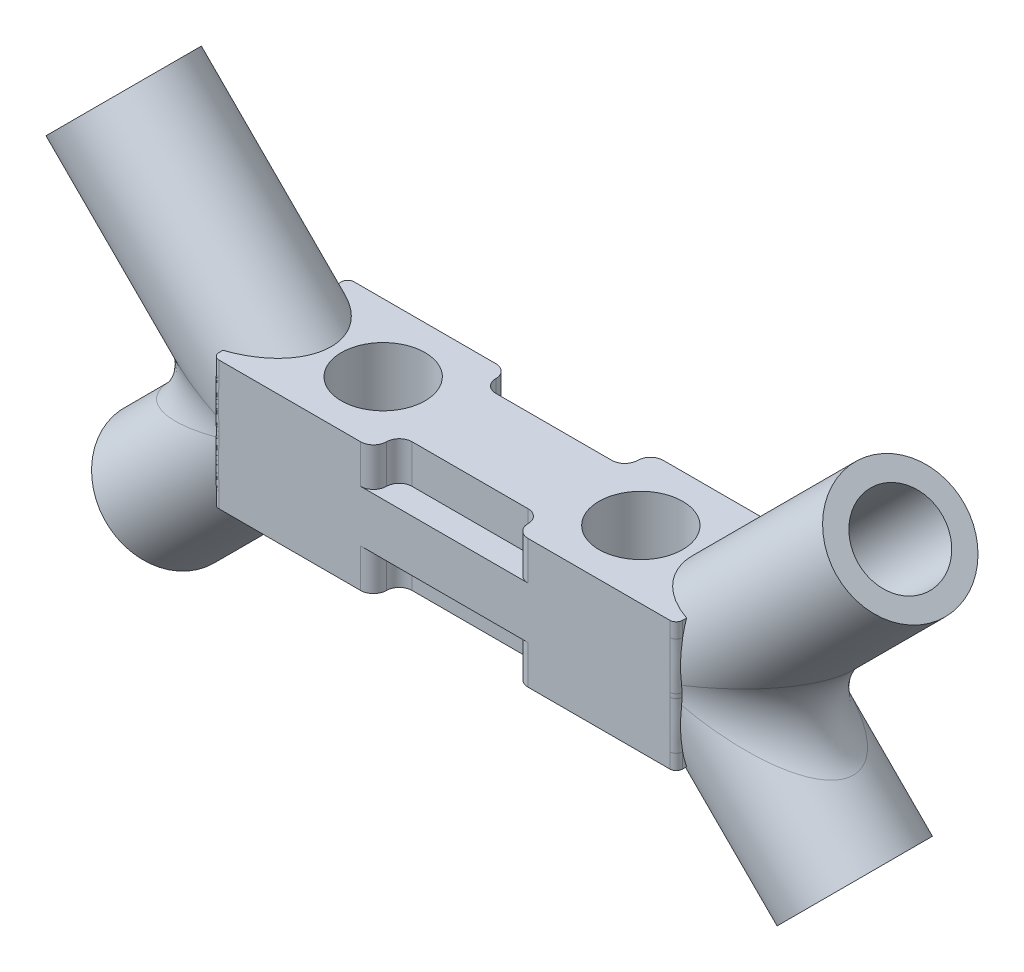
SolidWorks part; units mm, degrees
ref_plane "Alzado" through (0, 0, 0) normal (0, 0, 1) x (1, 0, 0)
ref_plane "Planta" through (0, 0, 0) normal (0, 1, 0) x (1, 0, 0)
ref_plane "Vista lateral" through (0, 0, 0) normal (1, 0, 0) x (0, 0, -1)
sketch "Croquis1" plane through (0, 0, 0) normal (0, 1, 0) x (1, 0, 0)
  line L0 (0, 0) -> (-36, 0) construction
  line L1 (-11, 6.5) -> (11, 6.5)
  line L3 (-11, -6.5) -> (11, -6.5)
  line L5 (-11, 6.5) -> (11, -6.5) construction
  line L6 (-11, -6.5) -> (11, 6.5) construction
  line L7 (-36, -10.5) -> (-36, 10.5)
  line L10 (0, 0) -> (0, -6.5) construction
  line L12 (36, -10.5) -> (36, 10.5)
  line L14 (-36, 10.5) -> (-11, 10.5)
  line L15 (-11, 10.5) -> (-11, 6.5)
  line L16 (-36, -10.5) -> (-11, -10.5)
  line L17 (-11, -10.5) -> (-11, -6.5)
  line L18 (36, 10.5) -> (11, 10.5)
  line L19 (11, 10.5) -> (11, 6.5)
  line L20 (36, -10.5) -> (11, -10.5)
  line L21 (11, -10.5) -> (11, -6.5)
  point P4 (0, 0)
  point P14 (-36, 0)
  point P16 (0, 6.5)
  dimension "D1" = 25
  dimension "D4" = 21
  dimension "D2" = 22
  dimension "D3" = 13
extrude "Saliente-Extruir2" add sketch "Croquis1" along normal mid plane 20
sketch "Croquis2" plane through (0, 0, 0) normal (0, 1, 0) x (1, 0, 0)
  line L0 (-36, -5) -> (-50.1421, -19.1421)
  line L2 (-36, -5) -> (-36, 5)
  line L3 (36, -5) -> (36, 5)
  line L4 (36, -10.5) -> (36, 10.5) construction
  line L5 (36, -5) -> (50.1421, -19.1421)
  line L6 (36, 5) -> (50.1421, 19.1421)
  line L7 (0, 0) -> (0, -6.5) construction
  line L8 (-11, -6.5) -> (11, -6.5) construction
  line L9 (-36, 5) -> (-50.1421, 19.1421)
  point P15 (36, 0)
  dimension "D2" = 10
  dimension "D5" = 45
  dimension "D6" = 45
  dimension "D7" = 20
ref_plane "Plano1" through (50.1421, 0, 0) normal (1, 0, 0) x (0, 0, -1)
sketch "Croquis22" plane through (0, 0, 0) normal (0, 0, 1) x (1, 0, 0)
  line L0 (-60.2843, 28.2843) -> (-32, 0)
  line L1 (-32, 0) -> (-53.2132, -21.2132)
  line L2 (-32, 0) -> (-36, 0) construction
  line L3 (-36, 10) -> (-36, -10) construction
  line L4 (32, 0) -> (53.2132, -21.2132)
  line L5 (60.2843, 28.2843) -> (32, 0)
  line L6 (0, 0) -> (0, -10) construction
  line L7 (-11, -10) -> (11, -10) construction
  dimension "D6" = 45
  dimension "D2" = 45
  dimension "D3" = 40
  dimension "D4" = 4
  dimension "D5" = 30
ref_plane "Plano2" through (-60.2843, 28.2843, 0) normal (0.7071, -0.7071, 0) x (-0.7071, -0.7071, 0)
sketch "Croquis33" plane through (-60.2843, 28.2843, 0) normal (0.7071, -0.7071, 0) x (-0.7071, -0.7071, 0)
  circle A0 centre (0, 0) radius 9.85
  dimension "D1" = 19.7
ref_plane "Plano3" through (60.2843, 28.2843, 0) normal (-0.7071, -0.7071, 0) x (0, 0, 1)
sketch "Croquis34" plane through (60.2843, 28.2843, 0) normal (-0.7071, -0.7071, 0) x (0, 0, 1)
  circle A0 centre (0, 0) radius 9.85
  dimension "D2" = 19.7
sketch "Croquis35" plane through (0, 0, 0) normal (0, 1, 0) x (1, 0, 0)
  line L0 (-20, 0) -> (20, 0) construction
  circle A0 centre (-20, 0) radius 6.5
  circle A1 centre (20, 0) radius 6.5
  point P4 (0, 0)
  dimension "D1" = 13
  dimension "D2" = 40
extrude "Huecos frontales" cut sketch "Croquis35" against normal mid plane 30 contours A1 | A0
extrude "Saliente-Extruir3" add sketch "Croquis33" along normal up to body separate body
extrude "Saliente-Extruir5" add sketch "Croquis34" along normal up to body separate body
ref_plane "Plano4" through (-53.2132, -21.2132, 0) normal (-0.7071, -0.7071, 0) x (0, 0, 1)
ref_plane "Plano5" through (53.2132, -21.2132, 0) normal (0.7071, -0.7071, 0) x (0, 0, -1)
sketch "Croquis36" plane through (-53.2132, -21.2132, 0) normal (-0.7071, -0.7071, 0) x (0, 0, 1)
  circle A0 centre (0, 0) radius 9.85
  dimension "D2" = 19.7
extrude "Saliente-Extruir6" add sketch "Croquis36" against normal up to body separate body
sketch "Croquis37" plane through (53.2132, -21.2132, 0) normal (0.7071, -0.7071, 0) x (0, 0, -1)
  circle A0 centre (0, 0) radius 9.85
  dimension "D1" = 19.7
extrude "Saliente-Extruir7" add sketch "Croquis37" against normal up to body separate body
fillet "Redondeo2" radius 2 8 edges at (11, 0, -10.5) (11, 0, -6.5) (-11, 0, -6.5) (-11, 0, -10.5) (11, 0, 6.5) (11, 0, 10.5) (-11, 0, 6.5) (-11, 0, 10.5)
fillet "Redondeo4" radius 1 4 edges at (-36, 0, 10.5) (36, 0, 10.5) (-36, 0, -10.5) (36, 0, -10.5)
sketch "Croquis38" plane through (-44.2843, 44.2843, 0) normal (-0.7071, 0.7071, 0) x (0, 0, 1)
  circle A0 centre (0, -22.6274) radius 6.5
  circle A1 centre (0, -22.6274) radius 9.85
  circle A2 centre (0, -22.6274) radius 9.85
  dimension "D2" = 13
  dimension "D1" = 0
extrude "Cortar-Extruir3" cut sketch "Croquis38" against normal blind 30 contours A0
sketch "Croquis40" plane through (-37.2132, -37.2132, 0) normal (-0.7071, -0.7071, 0) x (0, 0, 1)
  circle A0 centre (0, 22.6274) radius 6.53
  circle A1 centre (0, 22.6274) radius 9.85
  circle A2 centre (0, 22.6274) radius 9.85
  dimension "D2" = 3.32
  dimension "D3" = 13.06
  dimension "D1" = 0
extrude "Cortar-Extruir4" cut sketch "Croquis40" against normal blind 20 contours A0
sketch "Croquis41" plane through (44.2843, 44.2843, 0) normal (0.7071, 0.7071, 0) x (0, 0, -1)
  circle A0 centre (0, -22.6274) radius 6.52
  circle A1 centre (0, -22.6274) radius 9.85
  circle A2 centre (0, -22.6274) radius 9.85
  dimension "D2" = 3.33
  dimension "D3" = 13.04
  dimension "D1" = 0
extrude "Cortar-Extruir5" cut sketch "Croquis41" against normal blind 30 contours A0
sketch "Croquis42" plane through (37.2132, -37.2132, 0) normal (0.7071, -0.7071, 0) x (0, 0, -1)
  circle A0 centre (0, 22.6274) radius 6.52
  circle A1 centre (0, 22.6274) radius 9.85 construction
  circle A2 centre (0, 22.6274) radius 9.85
  dimension "D1" = 3.33
extrude "Cortar-Extruir6" cut sketch "Croquis42" against normal blind 20 contours A0
fillet "Redondeo6" radius 10 9 edges at (-36, 0.1595, 9.4683) (-36, -0.1595, 9.4683) (-36, 0, 9.5) (-36, -4, -9.85) (-36, 4, -9.85) (-36, 0, -9.5) (-36, 0.1595, -9.4683) (-45.93, 0, 0) (-36, -0.1595, -9.4683)
fillet "Redondeo7" radius 10 9 edges at (36, -4, 9.85) (36, 4, 9.85) (36, 0, 9.5) (36, 0.1595, -9.4683) (36, -0.1595, -9.4683) (36, 0, -9.5) (36, 0.1595, 9.4683) (45.93, 0, 0) (36, -0.1595, 9.4683)
sketch "Croquis44" plane through (0, 0, 0) normal (0, 0, 1) x (1, 0, 0)
  line L0 (13, 10) -> (13, -10) construction
  line L1 (-13, -4) -> (13, -4)
  line L2 (-13, -4) -> (-13, 4)
  line L3 (-13, 4) -> (13, 4)
  line L4 (13, -4) -> (13, 4)
  line L5 (-13, -4) -> (13, 4) construction
  line L6 (-13, 4) -> (13, -4) construction
  point P0 (0, 0)
  dimension "D1" = 8
extrude "Saliente-Extruir8" add sketch "Croquis44" along normal up to surface and the other way blind 10 up to face at (-29.5098, 0.4201, 10.5)
